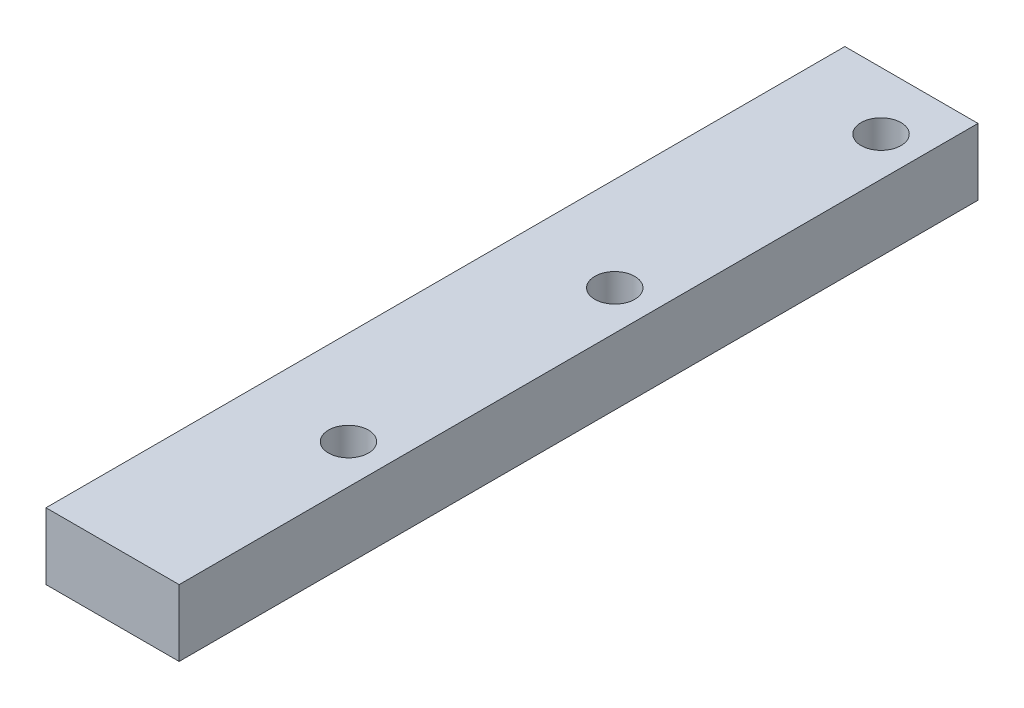
SolidWorks part; units mm, degrees
material "ABS"
ref_plane "Front Plane" through (0, 0, 0) normal (0, 0, 1) x (1, 0, 0)
ref_plane "Top Plane" through (0, 0, 0) normal (0, 1, 0) x (1, 0, 0)
ref_plane "Right Plane" through (0, 0, 0) normal (1, 0, 0) x (0, 0, -1)
sketch "Sketch1" plane through (0, 0, 0) normal (0, 0, 1) x (1, 0, 0)
  line L0 (20, 20.188) -> (0, 20.188)
  line L1 (0, 20.188) -> (0, 10.188)
  line L5 (20, 10.188) -> (20, 20.188)
  line L6 (0, 10.188) -> (20, 10.188)
  dimension "D1" = 20
  dimension "D2" = 10
  dimension "D3" = 10
extrude "Boss-Extrude1" add sketch "Sketch1" along normal blind 120
sketch "Sketch2" plane through (0, 20.188, 0) normal (0, 1, 0) x (1, 0, 0)
  circle A0 centre (14.1086, -8.6737) radius 3
extrude "Cut-Extrude1" cut sketch "Sketch2" against normal blind 140
pattern_linear "LPattern1" count 4 spacing 40 along (0, 0, 1) of "Cut-Extrude1"
